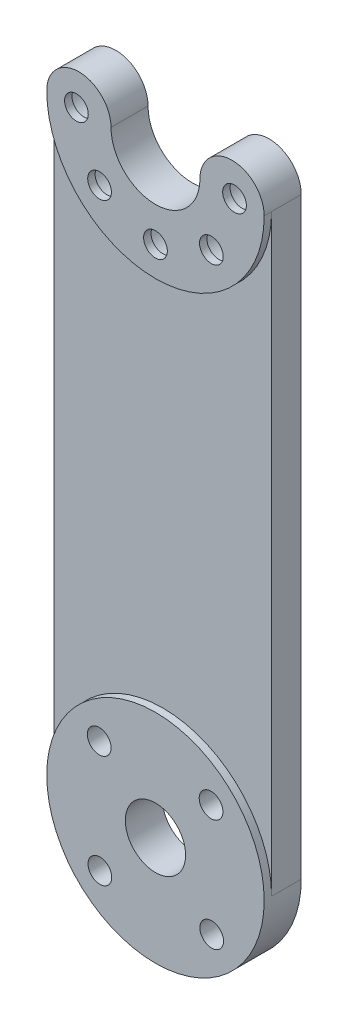
SolidWorks part; units mm, degrees
ref_plane "Plano frontal" through (0, 0, 0) normal (0, 0, 1) x (1, 0, 0)
ref_plane "Plano superior" through (0, 0, 0) normal (0, 1, 0) x (1, 0, 0)
ref_plane "Plano direito" through (0, 0, 0) normal (1, 0, 0) x (0, 0, -1)
sketch "Esboço1" plane through (0, 0, 0) normal (0, 0, 1) x (1, 0, 0)
  arc A2 (-4.5, 0) -> (4.5, 0) centre (0, 0) ccw
  arc A3 (11, 0) -> (-11, 0) centre (0, 0) cw
  arc A4 (-4, 0) -> (4, 0) centre (0, 0) ccw construction
  arc A5 (11, 0) -> (4.5, 0) centre (7.75, 0) ccw
  arc A6 (-4.5, 0) -> (-11, 0) centre (-7.75, 0) ccw
  arc A9 (-11, 0) -> (11, 0) centre (0, 0) ccw construction
  dimension "D1" = 0.5
extrude "Ressalto-extrusão1" add sketch "Esboço1" against normal offset from surface (0.75 mm away) 2 offset beyond the face yes
sketch "Esboço3" plane through (0, 0, -0.75) normal (0, 0, -1) x (-1, 0, 0)
  line L0 (-11, 0) -> (-11, -60)
  line L2 (11, -60) -> (11, 0)
  arc A0 (11, 0) -> (4.5, 0) centre (7.75, 0) ccw construction
  arc A1 (-4.5, 0) -> (4.5, 0) centre (0, 0) ccw construction
  arc A2 (-4.5, 0) -> (-11, 0) centre (-7.75, 0) ccw construction
  arc A3 (11, 0) -> (4.5, 0) centre (7.75, 0) ccw
  arc A4 (-4.5, 0) -> (4.5, 0) centre (0, 0) ccw
  arc A5 (-4.5, 0) -> (-11, 0) centre (-7.75, 0) ccw
  arc A9 (-11, -60) -> (11, -60) centre (0, -60) ccw
extrude "Ressalto-extrusão2" add sketch "Esboço3" along normal blind 3
hole_wizard "Rebaixo para SHCS M21" positions "Sketch1" profile "Sketch2" counterbore size "M2" standard "Ansi Metric" end condition up to next
sketch "Sketch1" plane through (0, 0, -3.75) normal (0, 0, -1) x (-1, 0, 0)
  line L0 (0, 0) -> (-8, 0) construction
  line L1 (0, 0) -> (-5.6569, -5.6569) construction
  line L2 (0, 0) -> (0, -8) construction
  line L3 (0, 0) -> (5.6569, -5.6569) construction
  line L4 (0, 0) -> (8, 0) construction
  arc A0 (-9, 0) -> (-7, 0) centre (-8, 0) ccw construction
  point P0 (-8, 0)
  point P16 (-5.6569, -5.6569)
  point P18 (0, -8)
  point P20 (5.6569, -5.6569)
  point P22 (8, 0)
  dimension "D1" = 5
sketch "Sketch2" plane through (8, 0, -3.75) normal (1, 0, 0) x (0, 1, 0)
  line L0 (0, 0) -> (0, 3.75)
  line L1 (0, 3.75) -> (1.2, 3.75)
  line L3 (1.2, 3.75) -> (1.2, 3)
  line L4 (1.2, 3) -> (2.2, 3)
  line L5 (2.2, 3) -> (2.2, 0)
  line L7 (2.2, 0) -> (0, 0)
  line L11 (0, -6.35) -> (0, 107.95) construction
  dimension "Thru Hole Dia." = 2.4
  dimension "Thru Hole Depth" = 3.75
  dimension "C'Bore Dia." = 4.4
  dimension "C'Bore Depth" = 3
sketch "Esboço4" plane through (0, 0, -0.75) normal (0, 0, 1) x (1, 0, 0)
  circle A0 centre (0, -60) radius 11
  arc A1 (-11, -60) -> (11, -60) centre (0, -60) ccw construction
extrude "Ressalto-extrusão3" add sketch "Esboço4" along normal up to surface (0.75 mm away)
sketch "Esboço5" plane through (0, 0, -3.75) normal (0, 0, -1) x (-1, 0, 0)
  circle A0 centre (0, -60) radius 3.05 construction
  circle A1 centre (0, -60) radius 3.05
extrude "Corte-extrusão1" cut sketch "Esboço5" against normal through all
hole_wizard "Rebaixo para parafuso com cabeça redonda de M21" positions "Esboço6" profile "Esboço7" counterbore size "M2" standard "DIN" end condition up to next
sketch "Esboço6" plane through (0, 0, -3.75) normal (0, 0, -1) x (-1, 0, 0)
  circle A0 centre (5.6247, -65.6888) radius 0.8 construction
  point P0 (5.6247, -65.6888)
  point P3 (0, 0)
sketch "Esboço7" plane through (-5.6247, -65.6888, -3.75) normal (1, 0, 0) x (0, 1, 0)
  line L0 (0, 0) -> (0, 3.75)
  line L1 (0, 3.75) -> (1.2, 3.75)
  line L3 (1.2, 3.75) -> (1.2, 1.4)
  line L4 (1.2, 1.4) -> (2.2, 1.4)
  line L5 (2.2, 1.4) -> (2.2, 0)
  line L7 (2.2, 0) -> (0, 0)
  line L11 (0, -6.35) -> (0, 107.95) construction
  dimension "Thru Hole Dia." = 2.4
  dimension "Thru Hole Depth" = 3.75
  dimension "C'Bore Dia." = 4.4
  dimension "C'Bore Depth" = 1.4
pattern_circular "PadrãoCircular1" count 4 over 360 about axis through (0, -60, -3.75) along (0, 0, -1) of "Rebaixo para parafuso com cabeça redonda de M21"
